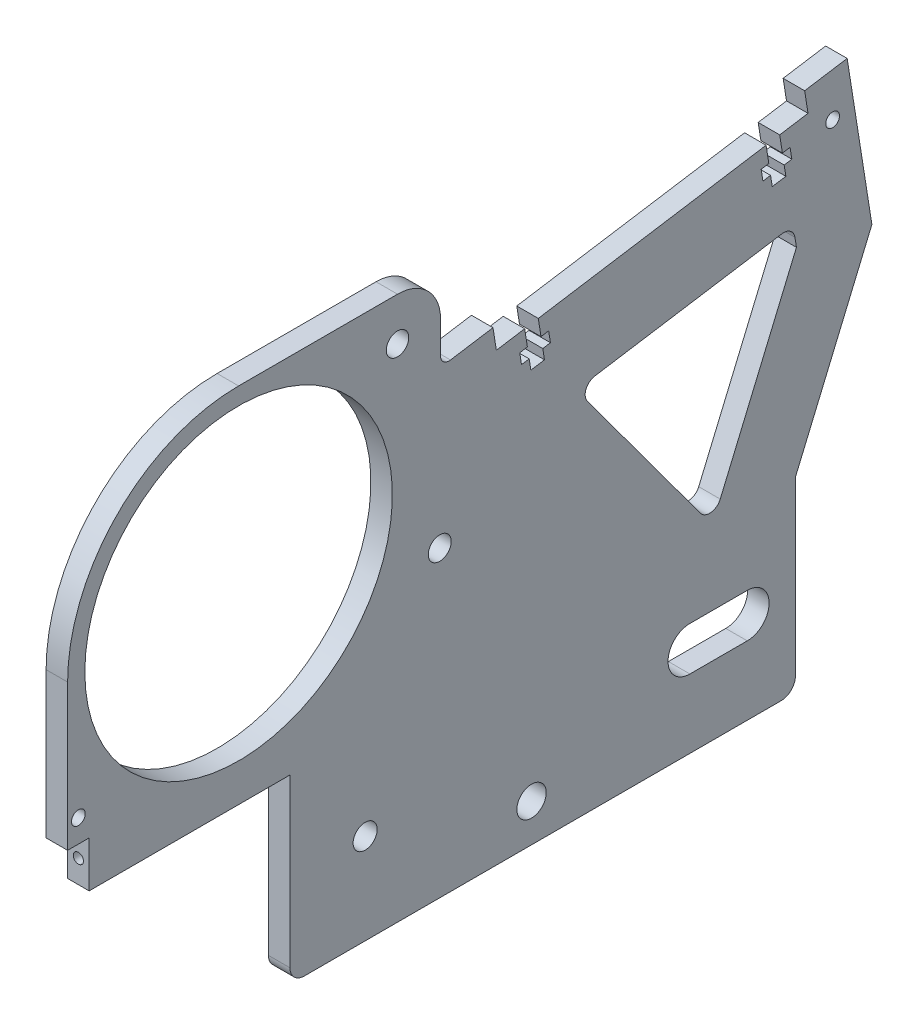
SolidWorks part; units mm, degrees
ref_plane "Front Plane" through (0, 0, 0) normal (0, 0, 1) x (1, 0, 0)
ref_plane "Top Plane" through (0, 0, 0) normal (0, 1, 0) x (1, 0, 0)
ref_plane "Right Plane" through (0, 0, 0) normal (1, 0, 0) x (0, 0, -1)
sketch "Sketch1" plane through (0, 0, 0) normal (1, 0, 0) x (0, 0, -1)
  line L0 (-28.1703, 0) -> (77.3828, 0)
  line L1 (80.5578, 3.175) -> (80.5578, 38.5047)
  line L2 (-80.5578, 82.55) -> (-80.5578, 50.292)
  line L3 (-7.5328, 120.4) -> (-42.7078, 120.4) construction
  line L4 (-75.7953, 50.292) -> (-75.7953, 40.132)
  line L5 (69.8898, 20.066) -> (57.1898, 20.066) construction
  line L6 (69.8898, 15.2273) -> (57.1898, 15.2273)
  line L7 (-75.7953, 40.132) -> (-31.3453, 40.132)
  line L8 (-7.5328, 120.4) -> (-42.7078, 120.4)
  line L9 (80.5578, 38.5047) -> (80.5578, 41.307)
  line L10 (-31.3453, 40.132) -> (-31.3453, 3.175)
  line L11 (-80.5578, 50.292) -> (-75.7953, 50.292)
  line L12 (69.8898, 24.9047) -> (57.1898, 24.9047)
  line L15 (77.5375, 89.4263) -> (36.1485, 82.8709) construction
  line L16 (34.5006, 78.856) -> (59.5216, 44.8808) construction
  line L17 (63.9057, 45.3965) -> (80.7745, 85.2255) construction
  line L18 (80.7745, 85.2255) -> (80.4436, 87.3149) construction
  line L19 (77.5375, 89.4263) -> (36.1485, 82.8709)
  line L20 (34.5006, 78.856) -> (59.5216, 44.8808)
  line L21 (63.9057, 45.3965) -> (80.7745, 85.2255)
  line L22 (80.7745, 85.2255) -> (80.4436, 87.3149)
  line L25 (80.5578, 41.307) -> (97.4765, 81.2539) construction
  line L26 (97.4765, 81.2539) -> (92.0007, 115.8264) construction
  line L27 (92.0007, 115.8264) -> (82.593, 114.3363) construction
  line L28 (82.593, 114.3363) -> (83.338, 109.6325) construction
  line L29 (83.338, 109.6325) -> (77.0662, 108.6391) construction
  line L30 (80.5578, 41.307) -> (97.4765, 81.2539)
  line L31 (97.4765, 81.2539) -> (92.0007, 115.8264)
  line L32 (92.0007, 115.8264) -> (82.593, 114.3363)
  line L33 (82.593, 114.3363) -> (83.338, 109.6325)
  line L34 (83.338, 109.6325) -> (77.0662, 108.6391)
  line L35 (77.0662, 108.6391) -> (77.6672, 104.8447) construction
  line L36 (74.6567, 104.3679) -> (74.0557, 108.1623) construction
  line L37 (72.9633, 104.0996) -> (74.6567, 104.3679) construction
  line L38 (77.6672, 104.8447) -> (79.3605, 105.1129) construction
  line L39 (79.3605, 105.1129) -> (79.7529, 102.6355) construction
  line L40 (79.7529, 102.6355) -> (78.0595, 102.3673) construction
  line L41 (73.3557, 101.6223) -> (72.9633, 104.0996) construction
  line L42 (75.0491, 101.8905) -> (73.3557, 101.6223) construction
  line L43 (75.4216, 99.5385) -> (75.0491, 101.8905) construction
  line L44 (78.432, 100.0154) -> (75.4216, 99.5385) construction
  line L45 (78.0595, 102.3673) -> (78.432, 100.0154) construction
  line L46 (74.0557, 108.1623) -> (23.6303, 100.1757) construction
  line L47 (77.0662, 108.6391) -> (77.6672, 104.8447)
  line L48 (74.6567, 104.3679) -> (74.0557, 108.1623)
  line L49 (72.9633, 104.0996) -> (74.6567, 104.3679)
  line L50 (77.6672, 104.8447) -> (79.3605, 105.1129)
  line L51 (79.3605, 105.1129) -> (79.7529, 102.6355)
  line L52 (79.7529, 102.6355) -> (78.0595, 102.3673)
  line L53 (73.3557, 101.6223) -> (72.9633, 104.0996)
  line L54 (75.0491, 101.8905) -> (73.3557, 101.6223)
  line L55 (75.4216, 99.5385) -> (75.0491, 101.8905)
  line L56 (78.432, 100.0154) -> (75.4216, 99.5385)
  line L57 (78.0595, 102.3673) -> (78.432, 100.0154)
  line L58 (74.0557, 108.1623) -> (23.6303, 100.1757)
  line L59 (23.6303, 100.1757) -> (24.2312, 96.3812) construction
  line L60 (24.2312, 96.3812) -> (25.9246, 96.6495) construction
  line L61 (25.9246, 96.6495) -> (26.317, 94.1721) construction
  line L62 (26.317, 94.1721) -> (24.6236, 93.9039) construction
  line L63 (24.6236, 93.9039) -> (24.9961, 91.5519) construction
  line L64 (24.9961, 91.5519) -> (21.9857, 91.0751) construction
  line L65 (21.9857, 91.0751) -> (21.6131, 93.4271) construction
  line L66 (21.6131, 93.4271) -> (19.9198, 93.1589) construction
  line L67 (19.9198, 93.1589) -> (19.5274, 95.6362) construction
  line L68 (19.5274, 95.6362) -> (21.2208, 95.9044) construction
  line L69 (21.2208, 95.9044) -> (20.6198, 99.6989) construction
  line L70 (20.6198, 99.6989) -> (14.348, 98.7055) construction
  line L71 (23.6303, 100.1757) -> (24.2312, 96.3812)
  line L72 (24.2312, 96.3812) -> (25.9246, 96.6495)
  line L73 (25.9246, 96.6495) -> (26.317, 94.1721)
  line L74 (26.317, 94.1721) -> (24.6236, 93.9039)
  line L75 (24.6236, 93.9039) -> (24.9961, 91.5519)
  line L76 (24.9961, 91.5519) -> (21.9857, 91.0751)
  line L77 (21.9857, 91.0751) -> (21.6131, 93.4271)
  line L78 (21.6131, 93.4271) -> (19.9198, 93.1589)
  line L79 (19.9198, 93.1589) -> (19.5274, 95.6362)
  line L80 (19.5274, 95.6362) -> (21.2208, 95.9044)
  line L81 (21.2208, 95.9044) -> (20.6198, 99.6989)
  line L82 (20.6198, 99.6989) -> (14.348, 98.7055)
  line L83 (14.348, 98.7055) -> (13.6029, 103.4094) construction
  line L84 (13.6029, 103.4094) -> (4.1952, 101.9194) construction
  line L85 (1.9922, 103.8009) -> (1.9922, 110.875) construction
  line L86 (14.348, 98.7055) -> (13.6029, 103.4094)
  line L87 (13.6029, 103.4094) -> (4.1952, 101.9194)
  line L88 (1.9922, 103.8009) -> (1.9922, 110.875)
  arc A0 (69.8898, 15.2273) -> (69.8898, 24.9047) centre (69.8898, 20.066) ccw
  circle A1 centre (-42.7078, 82.55) radius 31.5 construction
  circle A2 centre (69.8898, 20.066) radius 77.47 construction
  circle A3 centre (-78.1765, 55.372) radius 1.524
  arc A4 (57.1898, 24.9047) -> (57.1898, 15.2273) centre (57.1898, 20.066) ccw
  arc A5 (-42.7078, 120.4) -> (-80.5578, 82.55) centre (-42.7078, 82.55) ccw
  arc A6 (-28.1703, 0) -> (-31.3453, 3.175) centre (-28.1703, 3.175) cw
  arc A7 (77.3828, 0) -> (80.5578, 3.175) centre (77.3828, 3.175) ccw
  arc A10 (36.1485, 82.8709) -> (34.5006, 78.856) centre (36.5458, 80.3622) ccw construction
  circle A11 centre (-14.6922, 20.066) radius 2.667
  arc A12 (59.5216, 44.8808) -> (63.9057, 45.3965) centre (61.5669, 46.387) ccw construction
  arc A14 (80.4436, 87.3149) -> (77.5375, 89.4263) centre (77.9349, 86.9176) ccw construction
  arc A15 (36.1485, 82.8709) -> (34.5006, 78.856) centre (36.5458, 80.3622) ccw
  circle A16 centre (-42.7078, 82.55) radius 34.04
  arc A17 (59.5216, 44.8808) -> (63.9057, 45.3965) centre (61.5669, 46.387) ccw
  circle A18 centre (22.1378, 8.382) radius 3.2512
  arc A19 (80.4436, 87.3149) -> (77.5375, 89.4263) centre (77.9349, 86.9176) ccw
  circle A20 centre (1.8178, 67.06) radius 2.54
  circle A23 centre (88.7869, 105.6736) radius 1.524 construction
  circle A25 centre (88.7869, 105.6736) radius 1.524
  arc A26 (1.9922, 103.8009) -> (4.1952, 101.9194) centre (3.8972, 103.8009) ccw construction
  arc A27 (1.9922, 110.875) -> (-7.5328, 120.4) centre (-7.5328, 110.875) ccw construction
  circle A28 centre (-7.5328, 110.875) radius 2.4892 construction
  arc A29 (1.9922, 103.8009) -> (4.1952, 101.9194) centre (3.8972, 103.8009) ccw
  arc A30 (1.9922, 110.875) -> (-7.5328, 120.4) centre (-7.5328, 110.875) ccw
  circle A31 centre (-7.5328, 110.875) radius 2.4892
  point P13 (63.5398, 20.066)
  dimension "D4" = 9.6774
  dimension "D7" = 4.7625
  dimension "D8" = 63
  dimension "D9" = 6.5024
  dimension "D12" = 3.175
  dimension "D13" = 8.382
  dimension "D14" = 2.54
  dimension "D15" = 154.94
  dimension "D18" = 5.334
  dimension "D19" = 5.08
  dimension "D20" = 58.42
  dimension "D17" = 3.048
  dimension "D24" = 78.74
  dimension "D25" = 53.34
  dimension "D23" = 5.08
  dimension "D2" = 40.132
  dimension "D3" = 20.066
  dimension "D5" = 10.668
  dimension "D6" = 44.45
  dimension "D10" = 161.1156
  dimension "D11" = 95.25
  dimension "D21" = 12.7
  dimension "D22" = 10.16
  dimension "D16" = 2.3813
extrude "Boss-Extrude1" add sketch "Sketch1" along normal blind 4.7625
sketch "Sketch2" plane through (0, 0, 75.7953) normal (0, 0, 1) x (1, 0, 0)
  line L0 (0, 50.292) -> (0, 40.132) construction
  line L1 (4.7625, 40.132) -> (0, 40.132) construction
  circle A0 centre (2.3813, 45.212) radius 1.1303
  point P4 (0, 45.212)
  point P7 (2.3813, 40.132)
  dimension "D1" = 2.2606
extrude "Cut-Extrude1" cut sketch "Sketch2" against normal blind 6.35
